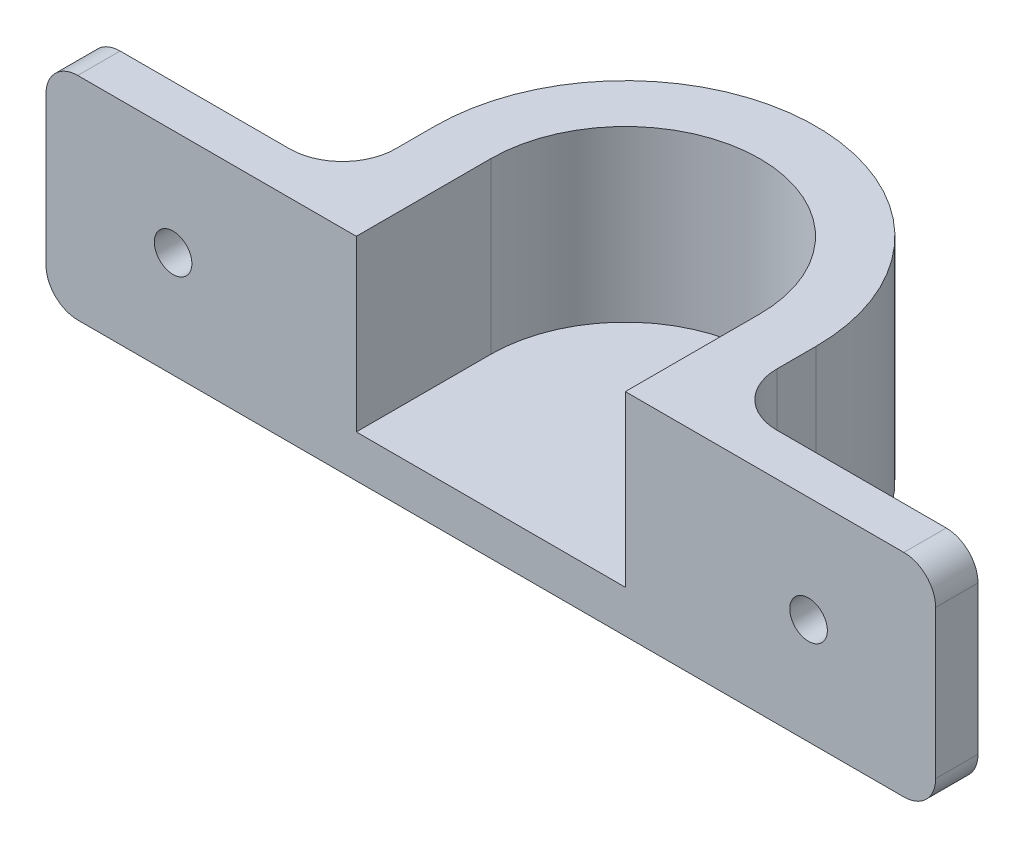
SolidWorks part; units mm, degrees
ref_plane "Front Plane" through (0, 0, 0) normal (0, 0, 1) x (1, 0, 0)
ref_plane "Top Plane" through (0, 0, 0) normal (0, 1, 0) x (1, 0, 0)
ref_plane "Right Plane" through (0, 0, 0) normal (1, 0, 0) x (0, 0, -1)
sketch "Sketch1" plane through (0, 0, 0) normal (0, 1, 0) x (1, 0, 0)
  line L0 (0, 0) -> (0, 4)
  line L1 (0, 4) -> (24, 4)
  line L2 (60, 4) -> (84, 4)
  line L3 (84, 4) -> (84, 0)
  line L6 (29.3, 12.7) -> (29.3, 0)
  line L7 (29.3, 0) -> (0, 0)
  line L8 (54.7, 12.7) -> (54.7, 0)
  line L9 (54.7, 0) -> (84, 0)
  line L10 (29.3, 12.7) -> (54.7, 12.7) construction
  line L11 (24, 12.7) -> (24, 4)
  line L12 (60, 12.7) -> (60, 4)
  line L13 (12, 4) -> (12, 0) construction
  line L14 (72, 4) -> (72, 0) construction
  arc A1 (54.7, 12.7) -> (29.3, 12.7) centre (42, 12.7) ccw
  arc A2 (60, 12.7) -> (24, 12.7) centre (42, 12.7) ccw
  dimension "D3" = 12.7
  dimension "D4" = 18
  dimension "D1" = 12.7
  dimension "D2" = 4
  dimension "D5" = 60
extrude "Boss-Extrude1" add sketch "Sketch1" along normal blind 20
sketch "Sketch2" plane through (0, 0, -4) normal (0, 0, -1) x (-1, 0, 0)
  line L0 (-42, 20) -> (-42, 0) construction
  line L1 (-24, 20) -> (-60, 20) construction
  line L2 (-60, 0) -> (-24, 0) construction
  line L3 (-72, 10) -> (-42, 10) construction
  line L4 (-42, 10) -> (-12, 10) construction
  circle A1 centre (-72, 10) radius 1.775
  circle A2 centre (-12, 10) radius 1.775
  dimension "D1" = 3.55
  dimension "D2" = 60
extrude "Cut-Extrude1" cut sketch "Sketch2" against normal through all
fillet "Fillet1" radius 3 4 edges at (0, 0, -2) (0, 20, -2) (84, 0, -2) (84, 20, -2)
fillet "Fillet2" radius 5 2 edges at (60, 10, -4) (24, 10, -4)
sketch "Sketch4" plane through (0, 0, 0) normal (0, -1, 0) x (1, 0, 0)
  line L0 (29.3, 0) -> (54.7, 0)
  line L1 (54.7, 0) -> (54.7, -12.7)
  line L2 (29.3, 0) -> (29.3, -12.7)
  arc A0 (29.3, -12.7) -> (54.7, -12.7) centre (42, -12.7) ccw
extrude "Boss-Extrude2" add sketch "Sketch4" against normal blind 4
